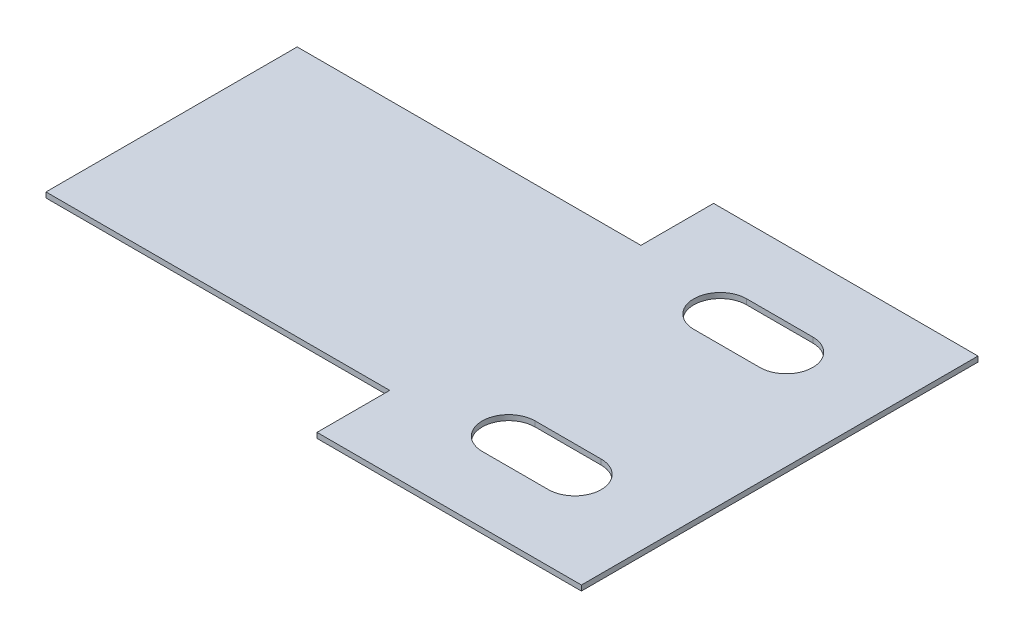
SolidWorks part; units mm, degrees
ref_plane "Front Plane" through (0, 0, 0) normal (0, 0, 1) x (1, 0, 0)
ref_plane "Top Plane" through (0, 0, 0) normal (0, 1, 0) x (1, 0, 0)
ref_plane "Right Plane" through (0, 0, 0) normal (1, 0, 0) x (0, 0, -1)
sketch "Sketch1" plane through (0, 0, 0) normal (0, 1, 0) x (1, 0, 0)
  line L20 (12.4712, 3.9627) -> (9.9712, 3.9627)
  line L21 (9.9712, 1.9627) -> (12.4712, 1.9627)
  line L22 (12.4712, -4.0373) -> (9.9712, -4.0373)
  line L23 (9.9712, -6.0373) -> (12.4712, -6.0373)
  line L24 (-6.7788, -5.7873) -> (6.2212, -5.7873)
  line L25 (6.2212, -5.7873) -> (6.2212, -8.5373)
  line L26 (6.2212, -8.5373) -> (16.2212, -8.5373)
  line L27 (16.2212, -8.5373) -> (16.2212, 6.4627)
  line L28 (16.2212, 6.4627) -> (6.2212, 6.4627)
  line L29 (6.2212, 6.4627) -> (6.2212, 3.7127)
  line L30 (6.2212, 3.7127) -> (-6.7788, 3.7127)
  line L31 (-6.7788, 3.7127) -> (-6.7788, -5.7873)
  arc A4 (9.9712, 3.9627) -> (9.9712, 1.9627) centre (9.9712, 2.9627) ccw
  arc A5 (12.4712, 1.9627) -> (12.4712, 3.9627) centre (12.4712, 2.9627) ccw
  arc A6 (9.9712, -4.0373) -> (9.9712, -6.0373) centre (9.9712, -5.0373) ccw
  arc A7 (12.4712, -6.0373) -> (12.4712, -4.0373) centre (12.4712, -5.0373) ccw
extrude "Boss-Extrude1" add sketch "Sketch1" along normal mid plane 0.2
